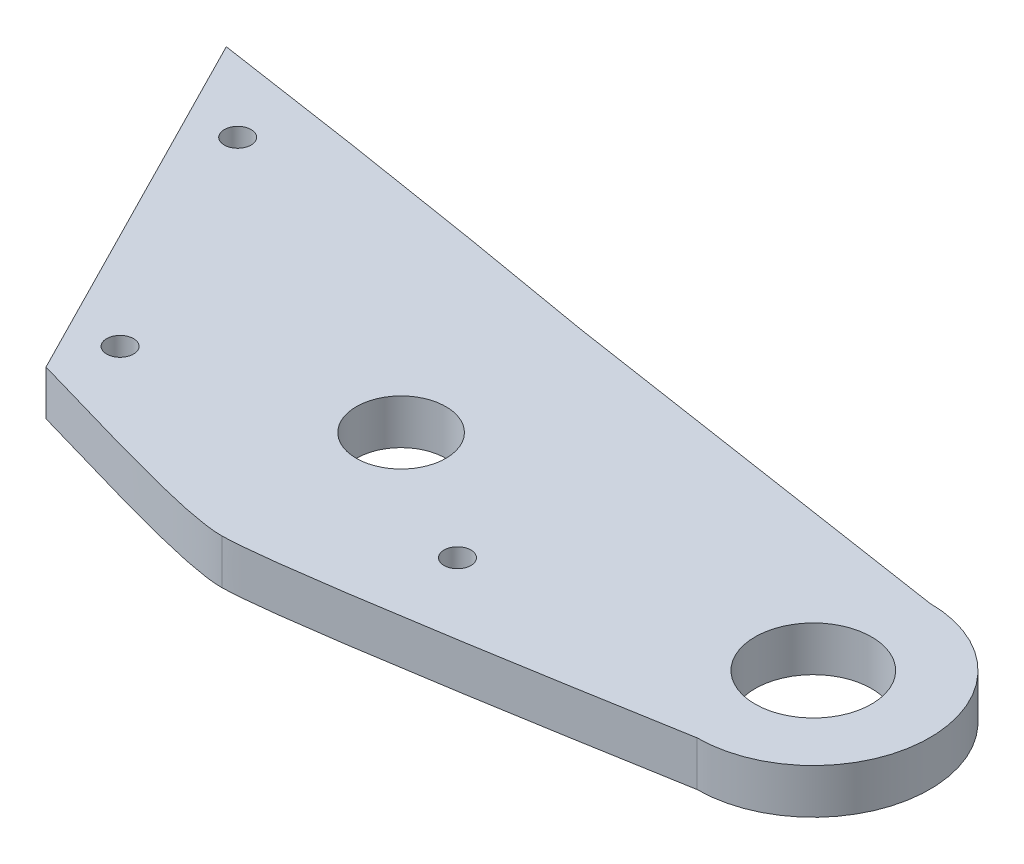
SolidWorks part; units mm, degrees
ref_plane "Front Plane" through (0, 0, 0) normal (0, 0, 1) x (1, 0, 0)
ref_plane "Top Plane" through (0, 0, 0) normal (0, 1, 0) x (1, 0, 0)
ref_plane "Right Plane" through (0, 0, 0) normal (1, 0, 0) x (0, 0, -1)
sketch "Sketch1" plane through (0, 0, 0) normal (0, 1, 0) x (1, 0, 0)
  line L0 (0, 0) -> (-300, 0) construction
  line L1 (0, 0) -> (46, 0) construction
  line L2 (-300, 0) -> (-300, 40) construction
  line L3 (-328.2843, 28.2843) -> (-271.7157, -28.2843) construction
  circle A0 centre (0, 0) radius 5
  circle A1 centre (46, 0) radius 6.5
  circle A2 centre (-300, 0) radius 40
  circle A3 centre (0, 0) radius 20
  circle A4 centre (46, 0) radius 13
  spline S0 degree 3 poles (-271.7157, -28.2843) (-189.2199, 54.2115) (-20, -20) (0, -20) knots 0 0 0 0 1 1 1 1
  spline S1 degree 3 poles (-328.2843, 28.2843) (-300, 56.5685) (-114.8731, 40.3783) (0, 20) knots 0 0 0 0 1 1 1 1
  spline S2 degree 2 poles (0, -20) (5.9085, -20) (46, -13) knots 0 0 0 1 1 1
  spline S3 degree 2 poles (0, 20) (0.0315, 20) (46, 13) knots 0 0 0 1 1 1
  dimension "D3" = 10
  dimension "D4" = 13
  dimension "D5" = 80
  dimension "D6" = 40
  dimension "D7" = 45
  dimension "D8" = 120
  dimension "D9" = 350
  dimension "D10" = 350
  dimension "D11" = 60
  dimension "D12" = 26
  dimension "D1" = 46
  dimension "D2" = 300
extrude "Boss-Extrude1" add sketch "Sketch1" along normal blind 20 and the other way blind 20 contours S1 A2 | S1 A2 S0 A3 | S3 A3 S0 A0 | S3 A3 S2 A4 | A4 A1 region at (-299.9271, 0, 0.2395) region at (-151.7179, 0, -19.1123) region at (-19.1932, 0, -3.0516) region at (26.0397, 0, 0.3418) region at (54.9324, 0, -8.9324)
ref_plane "Plane2" through (0, 20, 0) normal (0, 1, 0) x (1, 0, 0)
sketch "Sketch5" plane through (0, 20, 0) normal (0, 1, 0) x (1, 0, 0)
  line L0 (-47.037, 27.5275) -> (92.1208, 16.1646)
  line L1 (92.1208, 16.1646) -> (85.7247, -16.9188)
  line L2 (85.7247, -16.9188) -> (-17.2628, -30.9078)
  line L3 (-17.2628, -30.9078) -> (-47.037, 27.5275)
  line L4 (0, 0) -> (0, 89.1393) construction
  spline S0 degree 3 poles (-328.2843, 28.2843) (-300, 56.5685) (-114.8731, 40.3783) (0, 20) knots 0 0 0 0 1 1 1 1 construction
  dimension "D1" = 27
  dimension "D2" = 54.5
extrude "Cut-Extrude4" cut sketch "Sketch5" against normal blind 35
sketch "Sketch6" plane through (0, -20, 0) normal (0, -1, 0) x (-1, 0, 0)
  circle A1 centre (24.0052, -7.3569) radius 1.5
  circle A2 centre (-15.2511, -8.9603) radius 1.5
  circle A3 centre (37.6431, 19.409) radius 1.5
  dimension "D1" = 3
extrude "Cut-Extrude5" cut sketch "Sketch6" against normal blind 10
sketch "Sketch7" plane through (0, 20, 0) normal (0, 1, 0) x (1, 0, 0)
  line L0 (-47.037, 27.5275) -> (-26.1377, -13.4898)
  line L1 (-26.1377, -13.4898) -> (-379.5957, -92.5802)
  line L2 (-379.5957, -92.5802) -> (-321.5056, 137.2547)
  line L3 (-321.5056, 137.2547) -> (-47.037, 27.5275)
extrude "Cut-Extrude6" cut sketch "Sketch7" against normal blind 50
